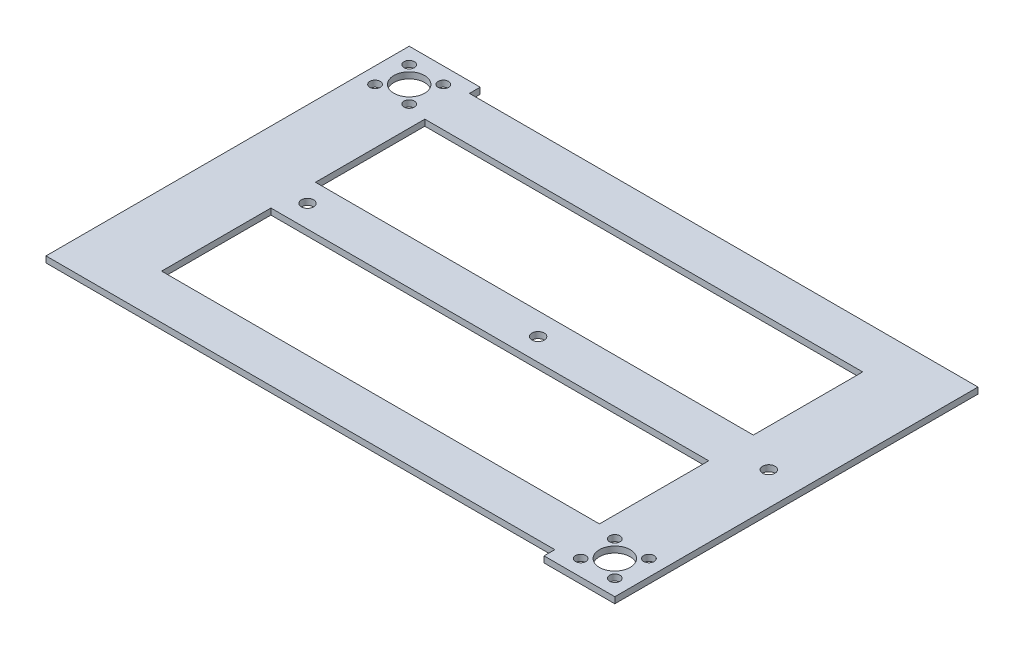
SolidWorks part; units mm, degrees
ref_plane "Front Plane" through (0, 0, 0) normal (0, 0, 1) x (1, 0, 0)
ref_plane "Top Plane" through (0, 0, 0) normal (0, 1, 0) x (1, 0, 0)
ref_plane "Right Plane" through (0, 0, 0) normal (1, 0, 0) x (0, 0, -1)
sketch "Sketch1" plane through (0, 0, 0) normal (0, 1, 0) x (1, 0, 0)
  line L0 (-95.0509, 92.8338) -> (57.8211, 92.8338) construction
  line L1 (-91.977, 142.8838) -> (-86.977, 142.8838) construction
  line L2 (-86.977, 142.8838) -> (-91.977, 142.8838) construction
  line L3 (67.7305, 150.1338) -> (82.2305, 150.1338)
  line L4 (-99.227, 35.5316) -> (-84.727, 35.5316)
  line L5 (-84.727, 35.5316) -> (62.7305, 35.5316)
  line L6 (-79.6432, 50.0316) -> (62.7305, 50.0316)
  line L7 (-79.6432, 150.1338) -> (67.7305, 150.1338)
  line L8 (-79.6432, 135.6338) -> (62.7305, 135.6338)
  line L9 (-79.6432, 100.0827) -> (62.7305, 100.0827)
  line L10 (-79.6432, 85.5827) -> (62.7305, 85.5827)
  line L17 (-84.6432, 153.6338) -> (-79.6432, 153.6338)
  line L18 (-84.6432, 153.6338) -> (-102.727, 153.6338)
  line L19 (-102.727, 100.0827) -> (-102.727, 153.6338)
  line L20 (-79.6432, 153.4321) -> (-79.6432, 150.1338)
  line L21 (-79.6432, 135.6338) -> (-79.6432, 100.0827)
  line L22 (-79.6432, 85.5827) -> (-79.6432, 50.0316)
  line L23 (-102.727, 85.5827) -> (-102.727, 35.5316)
  line L24 (-102.727, 35.5316) -> (-99.227, 35.5316)
  line L25 (67.7305, 32.0316) -> (62.7305, 32.0316)
  line L26 (67.7305, 32.0316) -> (85.7305, 32.0316)
  line L27 (85.7305, 50.0316) -> (85.7305, 32.0316)
  line L28 (62.7305, 32.0316) -> (62.7305, 35.5316)
  line L29 (62.7305, 50.0316) -> (62.7305, 85.5827)
  line L30 (62.7305, 100.0827) -> (62.7305, 135.6338)
  line L31 (85.7305, 50.0316) -> (85.7305, 85.5827)
  line L32 (85.7305, 100.0827) -> (85.7305, 150.1338)
  line L33 (85.7305, 150.1338) -> (82.2305, 150.1338)
  line L34 (-79.6432, 153.4321) -> (-79.6432, 153.6338)
  line L35 (0, -55) -> (0, 55) construction
  line L36 (-102.727, 100.0827) -> (-102.727, 85.5827)
  line L37 (85.7305, 100.0827) -> (85.7305, 85.5827)
  circle A0 centre (-91.977, 142.8838) radius 5
  circle A1 centre (74.9805, 42.7816) radius 5
  circle A2 centre (-86.427, 148.4338) radius 1.7
  circle A3 centre (-97.527, 148.4338) radius 1.7
  circle A4 centre (-86.427, 137.3338) radius 1.7
  circle A5 centre (-97.527, 137.3338) radius 1.7
  circle A6 centre (69.4305, 48.3316) radius 1.7
  circle A7 centre (80.5305, 48.3316) radius 1.7
  circle A8 centre (80.5305, 37.2316) radius 1.7
  circle A9 centre (69.4305, 37.2316) radius 1.7
  circle A10 centre (-75, 92.8338) radius 2
  circle A11 centre (0, 92.8338) radius 2
  circle A13 centre (75, 92.8338) radius 2
  dimension "D1" = 3.4
  dimension "D2" = 3.4
  dimension "D5" = 4
  dimension "D6" = 4
  dimension "D7" = 4
  dimension "D8" = 75
  dimension "D3" = 5
  dimension "D4" = 5
  dimension "D9" = 75
  dimension "D10" = 0
extrude "Boss-Extrude1" add sketch "Sketch1" along normal blind 2
